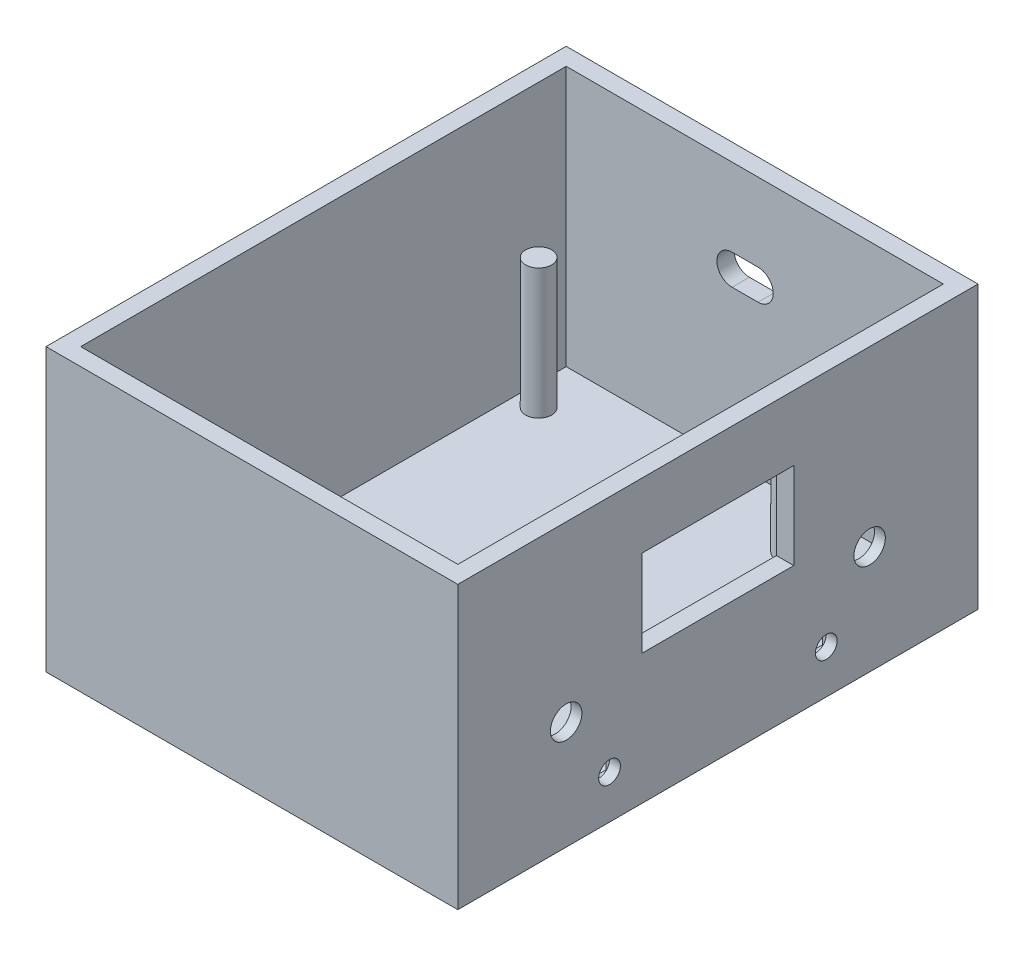
SolidWorks part; units mm, degrees
ref_plane "Front Plane" through (0, 0, 0) normal (0, 0, 1) x (1, 0, 0)
ref_plane "Top Plane" through (0, 0, 0) normal (0, 1, 0) x (1, 0, 0)
ref_plane "Right Plane" through (0, 0, 0) normal (1, 0, 0) x (0, 0, -1)
sketch "Sketch1" plane through (0, 0, 0) normal (0, 1, 0) x (1, 0, 0)
  line L1 (-47.5, -60) -> (47.5, -60)
  line L2 (-47.5, -60) -> (-47.5, 60)
  line L3 (-47.5, 60) -> (47.5, 60)
  line L4 (47.5, -60) -> (47.5, 60)
  line L5 (-47.5, -60) -> (47.5, 60) construction
  line L6 (-47.5, 60) -> (47.5, -60) construction
  point P0 (0, 0)
  dimension "D1" = 120
  dimension "D2" = 95
extrude "base dimensions" add sketch "Sketch1" along normal blind 5
sketch "Sketch2" plane through (0, 5, 0) normal (0, 1, 0) x (1, 0, 0)
  line L0 (47.5, -60) -> (47.5, 60) construction
  line L1 (-47.5, -60) -> (47.5, -60) construction
  line L2 (-47.5, 60) -> (-47.5, -60) construction
  line L3 (47.5, 60) -> (-47.5, 60) construction
  line L4 (47.5, -60) -> (47.5, 60)
  line L5 (-47.5, -60) -> (47.5, -60)
  line L6 (-47.5, 60) -> (-47.5, -60)
  line L7 (47.5, 60) -> (-47.5, 60)
  line L9 (-43.5, -56) -> (43.5, -56)
  line L10 (-43.5, -56) -> (-43.5, 56)
  line L11 (-43.5, 56) -> (43.5, 56)
  line L12 (43.5, -56) -> (43.5, 56)
  line L13 (-43.5, -56) -> (43.5, 56) construction
  line L14 (-43.5, 56) -> (43.5, -56) construction
  point P4 (0, 0)
  dimension "D1" = 4
  dimension "D2" = 4
extrude "wall height and depth" add sketch "Sketch2" along normal blind 60
sketch "Sketch3" plane through (0, 5, 0) normal (0, 1, 0) x (1, 0, 0)
  line L0 (-43.5, 56) -> (-43.5, -56) construction
  line L1 (-43.5, -56) -> (43.5, -56) construction
  circle A0 centre (-38.5, 44.645) radius 3
  circle A1 centre (-38.5, -36) radius 3
  circle A2 centre (32.62, -36) radius 3
  circle A3 centre (19.285, 44.645) radius 3
  dimension "D4" = 6
  dimension "D1" = 57.785
  dimension "D2" = 71.12
  dimension "D3" = 80.645
  dimension "D5" = 5
  dimension "D6" = 20
extrude "support pegs" add sketch "Sketch3" along normal blind 30
sketch "Sketch4" plane through (47.5, 0, 0) normal (1, 0, 0) x (0, 0, -1)
  line L0 (0, 71.0913) -> (0, -6.0913) construction
  line L1 (-17.5, 50) -> (17.5, 50)
  line L2 (-17.5, 50) -> (-17.5, 30)
  line L3 (-17.5, 30) -> (17.5, 30)
  line L4 (17.5, 50) -> (17.5, 30)
  line L5 (-17.5, 50) -> (17.5, 30) construction
  line L6 (-17.5, 30) -> (17.5, 50) construction
  line L7 (52.25, 0) -> (-52.25, 0) construction
  line L8 (-60, 65) -> (60, 65) construction
  circle A0 centre (-35, 25) radius 3.625
  circle A1 centre (-25, 10) radius 2.5
  circle A2 centre (25, 10) radius 2.5
  circle A3 centre (35, 25) radius 3.625
  point P0 (0, 40)
  point P12 (25, 10)
  dimension "D3" = 7.25
  dimension "D4" = 5
  dimension "D1" = 25
  dimension "D2" = 35
  dimension "D5" = 10
  dimension "D6" = 25
  dimension "D7" = 20
  dimension "D8" = 35
  dimension "D9" = 25
extrude "front holes" cut sketch "Sketch4" against normal up to surface (4 mm away) up to face at (43.5, 35, 0)
sketch "Sketch6" plane through (43.5, 0, 0) normal (-1, 0, 0) x (0, 0, 1)
  line L0 (0, -35.75) -> (0, 35.75) construction
  line L1 (-41.75, 31.375) -> (-28.25, 31.375)
  line L2 (-41.75, 31.375) -> (-41.75, 18.625)
  line L3 (-41.75, 18.625) -> (-28.25, 18.625)
  line L4 (-28.25, 31.375) -> (-28.25, 18.625)
  line L5 (-41.75, 31.375) -> (-28.25, 18.625) construction
  line L6 (-41.75, 18.625) -> (-28.25, 31.375) construction
  line L7 (-28.15, 6.85) -> (-21.85, 6.85)
  line L8 (-28.15, 6.85) -> (-28.15, 13.15)
  line L9 (-28.15, 13.15) -> (-21.85, 13.15)
  line L10 (-21.85, 6.85) -> (-21.85, 13.15)
  line L11 (-28.15, 6.85) -> (-21.85, 13.15) construction
  line L12 (-28.15, 13.15) -> (-21.85, 6.85) construction
  line L13 (28.15, 13.15) -> (21.85, 6.85) construction
  line L14 (28.15, 6.85) -> (21.85, 13.15) construction
  line L15 (41.75, 18.625) -> (28.25, 31.375) construction
  line L16 (41.75, 31.375) -> (28.25, 18.625) construction
  line L17 (21.85, 6.85) -> (21.85, 13.15)
  line L18 (28.15, 13.15) -> (21.85, 13.15)
  line L19 (28.15, 6.85) -> (28.15, 13.15)
  line L20 (28.15, 6.85) -> (21.85, 6.85)
  line L21 (28.25, 31.375) -> (28.25, 18.625)
  line L22 (41.75, 18.625) -> (28.25, 18.625)
  line L23 (41.75, 31.375) -> (41.75, 18.625)
  line L24 (41.75, 31.375) -> (28.25, 31.375)
  point P0 (-35, 25)
  point P6 (-25, 10)
  point P22 (25, 10)
  point P23 (35, 25)
  dimension "D1" = 13.5
  dimension "D2" = 12.75
  dimension "D3" = 6.3
extrude "en and b inlay" cut sketch "Sketch6" against normal blind 1.5
sketch "screen mounting layout" plane through (43.5, 0, 0) normal (-1, 0, 0) x (0, 0, 1)
  line L0 (0, -35.75) -> (0, 35.75) construction
  line L8 (-15.265, 24.85) -> (15.265, 24.85) construction
  line L9 (-15.265, 24.85) -> (-15.265, 53.46) construction
  line L10 (-15.265, 53.46) -> (15.265, 53.46) construction
  line L11 (15.265, 24.85) -> (15.265, 53.46) construction
  line L12 (-15.265, 24.85) -> (15.265, 53.46) construction
  line L13 (-15.265, 53.46) -> (15.265, 24.85) construction
  line L14 (-15.265, 23.3) -> (15.265, 23.3) construction
  line L15 (17.5, 30) -> (-17.5, 30) construction
  circle A0 centre (-15.265, 53.46) radius 1.55 construction
  circle A1 centre (-15.265, 24.85) radius 1.55 construction
  circle A2 centre (15.265, 24.85) radius 1.55 construction
  circle A3 centre (15.265, 53.46) radius 1.55 construction
  point P8 (0, 39.155)
  dimension "D3" = 3.1
  dimension "D4" = 3.1
  dimension "D1" = 30.53
  dimension "D2" = 28.61
  dimension "D5" = 6.7
sketch "Sketch9" plane through (0, 0, -56) normal (0, 0, 1) x (1, 0, 0)
  line L0 (-5.236, 43.5) -> (0.764, 43.5) construction
  line L1 (-5.236, 47) -> (0.764, 47)
  line L2 (-5.236, 40) -> (0.764, 40)
  line L3 (43.5, 5) -> (-43.5, 5) construction
  line L4 (-43.5, 65) -> (-43.5, 5) construction
  arc A0 (-5.236, 47) -> (-5.236, 40) centre (-5.236, 43.5) ccw
  arc A1 (0.764, 40) -> (0.764, 47) centre (0.764, 43.5) ccw
  point P2 (-2.236, 43.5)
  dimension "D2" = 3.5
  dimension "D1" = 6
  dimension "D3" = 35
  dimension "D4" = 41.264
extrude "usb slot" cut sketch "Sketch9" against normal through all
